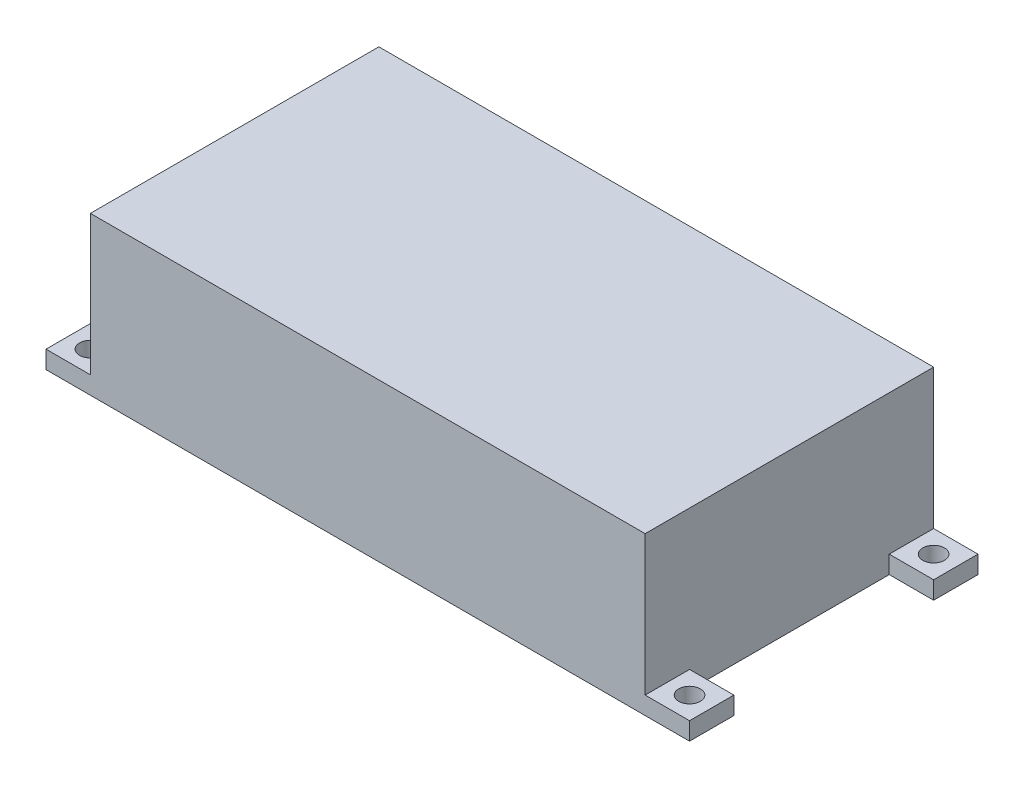
SolidWorks part; units mm, degrees
ref_plane "Front Plane" through (0, 0, 0) normal (0, 0, 1) x (1, 0, 0)
ref_plane "Top Plane" through (0, 0, 0) normal (0, 1, 0) x (1, 0, 0)
ref_plane "Right Plane" through (0, 0, 0) normal (1, 0, 0) x (0, 0, -1)
sketch "Sketch1" plane through (0, 0, 0) normal (0, 1, 0) x (1, 0, 0)
  line L0 (-1.5875, 39.6875) -> (77.7875, 39.6875)
  line L1 (0, 0) -> (76.2, 0)
  line L2 (0, 0) -> (0, 38.1)
  line L3 (0, 38.1) -> (76.2, 38.1)
  line L4 (76.2, 0) -> (76.2, 38.1)
  line L5 (77.7875, 39.6875) -> (77.7875, -1.5875)
  line L6 (-1.5875, 39.6875) -> (-1.5875, -1.5875)
  line L7 (-1.5875, -1.5875) -> (77.7875, -1.5875)
  dimension "D1" = 38.1
  dimension "D2" = 76.2
  dimension "D3" = 1.5875
  dimension "D4" = 1.5875
  dimension "D5" = 1.5875
  dimension "D6" = 1.5875
extrude "Boss-Extrude1" add sketch "Sketch1" along normal blind 20.955
sketch "Sketch2" plane through (0, 20.955, 0) normal (0, 1, 0) x (1, 0, 0)
  line L1 (-1.5875, 39.6875) -> (77.7875, 39.6875)
  line L2 (-1.5875, 39.6875) -> (-1.5875, -1.5875)
  line L3 (-1.5875, -1.5875) -> (77.7875, -1.5875)
  line L4 (77.7875, 39.6875) -> (77.7875, -1.5875)
extrude "Boss-Extrude2" add sketch "Sketch2" along normal blind 1.5875
sketch "Sketch3" plane through (0, 0, 0) normal (0, -1, 0) x (1, 0, 0)
  line L0 (38.1, 1.5875) -> (38.1, -39.6875) construction
  line L1 (77.7875, -39.6875) -> (84.1375, -39.6875)
  line L2 (77.7875, -39.6875) -> (77.7875, -33.3375)
  line L3 (77.7875, -33.3375) -> (84.1375, -33.3375)
  line L4 (84.1375, -39.6875) -> (84.1375, -33.3375)
  line L5 (-1.5875, 1.5875) -> (77.7875, 1.5875) construction
  line L6 (77.7875, -39.6875) -> (-1.5875, -39.6875) construction
  line L7 (-1.5875, -19.05) -> (77.7875, -19.05) construction
  line L8 (-1.5875, -39.6875) -> (-1.5875, 1.5875) construction
  line L9 (77.7875, 1.5875) -> (77.7875, -39.6875) construction
  line L10 (84.1375, 1.5875) -> (84.1375, -4.7625)
  line L11 (77.7875, -4.7625) -> (84.1375, -4.7625)
  line L12 (77.7875, 1.5875) -> (77.7875, -4.7625)
  line L13 (77.7875, 1.5875) -> (84.1375, 1.5875)
  line L14 (-1.5875, 1.5875) -> (-7.9375, 1.5875)
  line L15 (-1.5875, 1.5875) -> (-1.5875, -4.7625)
  line L16 (-1.5875, -4.7625) -> (-7.9375, -4.7625)
  line L17 (-7.9375, 1.5875) -> (-7.9375, -4.7625)
  line L18 (-7.9375, -39.6875) -> (-7.9375, -33.3375)
  line L19 (-1.5875, -33.3375) -> (-7.9375, -33.3375)
  line L20 (-1.5875, -39.6875) -> (-1.5875, -33.3375)
  line L21 (-1.5875, -39.6875) -> (-7.9375, -39.6875)
  circle A0 centre (80.9625, -36.5125) radius 1.55
  circle A1 centre (80.9625, -1.5875) radius 1.55
  circle A2 centre (-4.7625, -1.5875) radius 1.55
  circle A3 centre (-4.7625, -36.5125) radius 1.55
  dimension "D3" = 3.1
  dimension "D1" = 6.35
  dimension "D2" = 6.35
  dimension "D4" = 3.175
  dimension "D5" = 3.175
extrude "Boss-Extrude3" add sketch "Sketch3" against normal blind 2.54
sketch "Sketch4" plane through (0, 0, 0) normal (0, -1, 0) x (1, 0, 0)
  line L0 (76.2, -38.1) -> (0, -38.1) construction
  line L1 (-1.5875, -39.6875) -> (7.3025, -39.6875)
  line L2 (-1.5875, -39.6875) -> (-1.5875, -38.1)
  line L3 (-1.5875, -38.1) -> (7.3025, -38.1)
  line L4 (7.3025, -39.6875) -> (7.3025, -38.1)
  dimension "D1" = 8.89
extrude "Cut-Extrude1" cut sketch "Sketch4" against normal up to surface (20.955 mm away) up to face at (38.1, 20.955, -19.05)
sketch "Sketch5" plane through (0, 0, 0) normal (0, -1, 0) x (1, 0, 0)
  line L0 (-1.5875, -38.1) -> (-1.5875, -39.6875) construction
  line L1 (0, -38.1) -> (-1.5875, -38.1)
  line L2 (0, -38.1) -> (0, -39.6875)
  line L3 (0, -39.6875) -> (-1.5875, -39.6875)
  line L4 (-1.5875, -38.1) -> (-1.5875, -39.6875)
extrude "Boss-Extrude4" add sketch "Sketch5" against normal up to next
